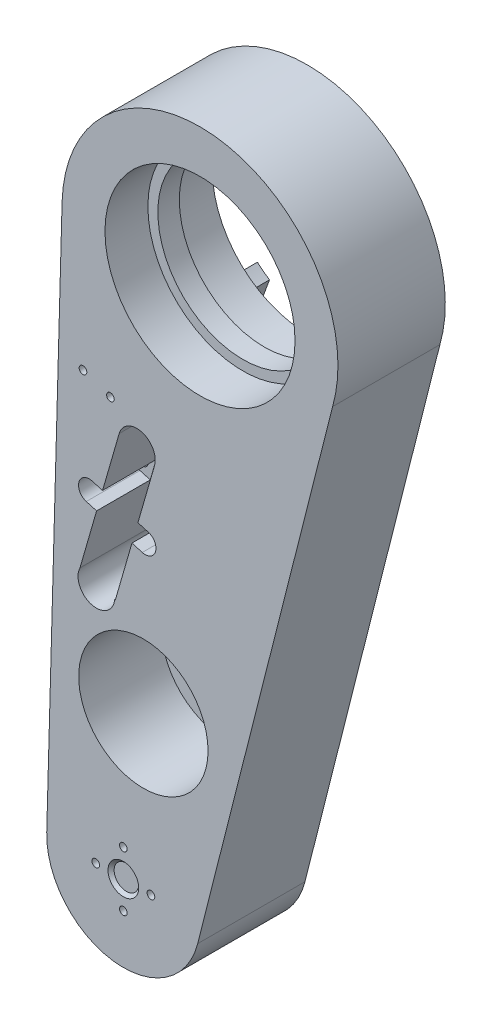
SolidWorks part; units mm, degrees
ref_plane "Ebene vorne" through (0, 0, 0) normal (0, 0, 1) x (1, 0, 0)
ref_plane "Ebene oben" through (0, 0, 0) normal (0, 1, 0) x (1, 0, 0)
ref_plane "Ebene rechts" through (0, 0, 0) normal (1, 0, 0) x (0, 0, -1)
sketch "Skizze1" plane through (0, 0, 0) normal (0, 0, 1) x (1, 0, 0)
  line L0 (-24.9904, 0.6931) -> (-19.9827, 181.2476)
  line L2 (68.9493, 170.3326) -> (24.2342, -6.1405)
  circle A0 centre (0, 0) radius 9
  circle A6 centre (0, 0) radius 25
  circle A7 centre (25, 180) radius 45
  circle A8 centre (25, 180) radius 28
  point P14 (0, 0)
  dimension "D1" = 18
  dimension "D3" = 50
  dimension "D5" = 90
  dimension "D7" = 56
  dimension "D4" = 180
  dimension "D6" = 25
extrude "Aufsatz-Linear austragen1" add sketch "Skizze1" along normal blind 35 contours A7 | A7 A6 | A6 A0 | A0 | A7 region at (11.8715, 85.5396, 0) region at (0.3368, 24.2906, 0) region at (68.6084, 168.9504, 0) region at (0, 0, 0)
sketch "Skizze2" plane through (0, 0, 35) normal (0, 0, 1) x (1, 0, 0)
  circle A0 centre (0, 0) radius 4
  dimension "D1" = 8
extrude "Schnitt-Linear austragen1" cut sketch "Skizze2" against normal blind 1 contours A0
chamfer "Fase1" distance 1 angle 45 1 edges at (4, 0, 35)
sketch "Skizze4" plane through (0, 0, 35) normal (0, 0, 1) x (1, 0, 0)
  arc A0 (-1.247, 8.9132) -> (-8.9132, 1.247) centre (0, 0) ccw
  circle A1 centre (9, 0) radius 1.25
  circle A2 centre (0, -9) radius 1.25
  circle A3 centre (-9, 0) radius 1.25
  circle A4 centre (0, 9) radius 1.25
  arc A5 (-8.9132, -1.247) -> (-1.247, -8.9132) centre (0, 0) ccw
  arc A6 (8.9132, 1.247) -> (1.247, 8.9132) centre (0, 0) ccw
  arc A7 (1.247, -8.9132) -> (8.9132, -1.247) centre (0, 0) ccw
  point P14 (0, 0)
  dimension "D1" = 18
  dimension "D2" = 4
  dimension "D3" = 2.5
extrude "Schnitt-Linear austragen2" cut sketch "Skizze4" against normal blind 15 contours A4 | A1 | A2 | A3 region at (0, 9, 35) region at (-9, 0, 35) region at (9, 0, 35) region at (0, -9, 35)
sketch "Skizze5" plane through (0, 0, 0) normal (0, 0, -1) x (-1, 0, 0)
  circle A0 centre (0, 0) radius 8
  circle A1 centre (8, 0) radius 1.25
  circle A2 centre (0, -8) radius 1.25
  circle A3 centre (-8, 0) radius 1.25
  circle A4 centre (0, 8) radius 1.25
  circle A5 centre (0, 0) radius 9.25
  point P14 (0, 0)
  dimension "D1" = 4
  dimension "D3" = 16
extrude "Schnitt-Linear austragen3" cut sketch "Skizze5" against normal blind 15 contours A0 A4 | A0 A4 | A0 A3 | A0 A3 | A0 A1 | A0 A1 | A0 A2 | A0 A2 region at (-7.4523, 0, 0) region at (-8.5125, 0, 0) region at (0, 7.4523, 0) region at (0, 8.5125, 0) region at (0, -8.5125, 0) region at (0, -7.4523, 0) region at (7.4523, 0, 0) region at (8.5125, 0, 0)
sketch "Skizze6" plane through (0, 0, 35) normal (0, 0, 1) x (1, 0, 0)
  line L1 (25, 182.9902) -> (0, 2.9902) construction
  circle A1 centre (6.5291, 50) radius 12.5
  dimension "D1" = 50
  dimension "D2" = 25
extrude "Schnitt-Linear austragen4" cut sketch "Skizze6" against normal blind 35
sketch "Skizze7" plane through (0, 0, 35) normal (0, 0, 1) x (1, 0, 0)
  circle A0 centre (6.5291, 50) radius 21.1
  dimension "D1" = 42.2
extrude "Schnitt-Linear austragen5" cut sketch "Skizze7" against normal offset from surface (27 mm away) 8 up to face at (19.0291, 50, 0)
sketch "Skizze8" plane through (0, 0, 8) normal (0, 0, 1) x (1, 0, 0)
  line L0 (6.5291, 50) -> (5.2968, 32.5434) construction
  arc A0 (5.7616, 67.4832) -> (-10.6728, 53.216) centre (6.5291, 50) ccw
  circle A1 centre (5.2968, 32.5434) radius 2
  circle A2 centre (-10.9274, 51.2323) radius 2
  circle A3 centre (7.7615, 67.4566) radius 2
  circle A4 centre (23.9857, 48.7677) radius 2
  arc A5 (24.0123, 50.7675) -> (9.7452, 67.2019) centre (6.5291, 50) ccw
  arc A6 (7.2966, 32.5168) -> (24.0123, 50.7675) centre (6.5291, 50) ccw
  arc A7 (-10.6728, 53.216) -> (3.3131, 32.7981) centre (6.5291, 50) ccw
  point P14 (6.5291, 50)
  dimension "D1" = 4
  dimension "D2" = 4
  dimension "D3" = 17.5
extrude "Schnitt-Linear austragen6" cut sketch "Skizze8" against normal blind 15 contours A4 | A3 | A1 | A2 | A2 | A4 region at (7.7615, 67.4566, 8) region at (-11.7533, 51.2906, 8) region at (23.1188, 48.8289, 8) region at (5.2968, 32.5434, 8)
sketch "Skizze9" plane through (0, 0, 0) normal (0, 0, -1) x (-1, 0, 0)
  circle A0 centre (-5.2968, 32.5434) radius 3.7
  circle A1 centre (-23.9857, 48.7677) radius 3.7
  circle A2 centre (-7.7615, 67.4566) radius 3.7
  circle A3 centre (10.9274, 51.2323) radius 3.7
  point P3 (-6.5291, 50)
  point P14 (-6.5291, 50)
  dimension "D1" = 7.4
  dimension "D2" = 4
extrude "Schnitt-Linear austragen7" cut sketch "Skizze9" against normal blind 4
sketch "Skizze10" plane through (0, 0, 35) normal (0, 0, 1) x (1, 0, 0)
  circle A0 centre (25, 180) radius 31
  dimension "D1" = 62
extrude "Schnitt-Linear austragen8" cut sketch "Skizze10" against normal blind 14
ref_plane "Ebene1" through (0, 0, 17.5) normal (0, 0, 1) x (1, 0, 0)
mirror "Spiegeln1" about plane through (0, 0, 17.5) normal (0, 0, 1) of "Schnitt-Linear austragen8"
sketch "Skizze11" plane through (0, 0, 0) normal (0, 0, 1) x (1, 0, 0)
  circle A1 centre (25.3541, 102.1802) radius 1.75
extrude "Schnitt-Linear austragen10" cut sketch "Skizze11" along normal blind 15
sketch "Skizze12" plane through (0, 0, 0) normal (0, 0, -1) x (-1, 0, 0)
  circle A1 centre (-25, 180) radius 32
  circle A4 centre (-9.1089, 136.6817) radius 2.1
  dimension "D3" = 64
extrude "Schnitt-Linear austragen11" cut sketch "Skizze12" against normal blind 20 contours A4 region at (9.1089, 136.6817, 0)
sketch "Sketch1" plane through (0, 0, 0) normal (0, 0, -1) x (-1, 0, 0)
  line L0 (-13.9792, 149.9577) -> (-5.0749, 153.2242) construction
  line L1 (-5.0749, 153.2242) -> (-22.2848, 146.9108) construction
  line L2 (-20.8178, 148.2745) -> (-16.2029, 135.6945)
  line L3 (-16.2029, 135.6945) -> (-25.776, 148.0094)
  line L4 (-25, 180) -> (-2.3558, 118.273) construction
  line L5 (-7.6743, 153.0961) -> (-3.0594, 140.5161)
  line L6 (-3.0594, 140.5161) -> (-3.721, 156.1001)
  circle A0 centre (-25, 180) radius 32
  dimension "D1" = 64
  dimension "D2" = 14
extrude "Boss-Extrude1" add sketch "Sketch1" along normal blind 5 contours A0 L3 L2 | A0 L5 L6 region at (20.9083, 143.9511, 0) region at (4.8096, 149.8568, 0)
sketch "Sketch2" plane through (0, 0, 0) normal (0, 0, -1) x (-1, 0, 0)
  circle A0 centre (-4.4016, 123.4949) radius 6
extrude "Cut-Extrude1" cut sketch "Sketch2" against normal blind 35
ref_plane "Plane1" through (0, 0, 30) normal (0, 0, -1) x (-1, 0, 0)
sketch "Sketch3" plane through (0, 0, 17.5) normal (0, 0, -1) x (-1, 0, 0)
  line L0 (14.468, 79.7139) -> (1.3635, 125.1573)
  line L1 (-10.1667, 121.8324) -> (2.9378, 76.3889)
  circle A0 centre (-4.4016, 123.4949) radius 6 construction
  circle A1 centre (-4.4016, 123.4949) radius 6
  circle A2 centre (8.7029, 78.0514) radius 6
  dimension "D1" = 12
extrude "Cut-Extrude2" cut sketch "Sketch3" along normal blind 8 contours A2 L0 L1 | A2 region at (-2.1506, 100.7731, 17.5) region at (-8.7029, 78.0514, 17.5)
sketch "Sketch4" plane through (0, 0, 35) normal (0, 0, 1) x (1, 0, 0)
  circle A2 centre (-8.7869, 78.1376) radius 6
extrude "Cut-Extrude3" cut sketch "Sketch4" against normal up to surface (25.5 mm away) up to face at (-2.9819, 97.8906, 9.5)
sketch "Skizze14" plane through (0, 0, 0) normal (0, 0, -1) x (-1, 0, 0)
  circle A0 centre (-59.0996, 191.6681) radius 1.65
  circle A1 centre (4.4449, 200.7123) radius 1.655
  circle A2 centre (-26.5283, 29.0181) radius 1.65
  circle A3 centre (18.5472, 35.4337) radius 1.65
extrude "Schnitt-Linear austragen12" cut sketch "Skizze14" against normal blind 15
sketch "Skizze16" plane through (0, 0, 35) normal (0, 0, 1) x (1, 0, 0)
  circle A3 centre (-13.1725, 137.1867) radius 1.25
  circle A4 centre (-4.2165, 134.0181) radius 1.25
extrude "Schnitt-Linear austragen14" cut sketch "Skizze16" against normal blind 6
sketch "Skizze17" plane through (0, 0, 21) normal (0, 0, 1) x (1, 0, 0)
  circle A0 centre (25, 180) radius 27.75
  dimension "D1" = 55.5
extrude "Schnitt-Linear austragen15" cut sketch "Skizze17" against normal blind 10
sketch "Sketch5" plane through (0, 0, 35) normal (0, 0, 1) x (1, 0, 0)
  line L0 (-14.1424, 80.8429) -> (-1.3635, 125.1573)
  line L1 (-1.3635, 125.1573) -> (10.1667, 121.8324)
  line L2 (10.1667, 121.8324) -> (-2.6122, 77.5179)
  line L3 (10.1667, 121.8324) -> (-2.9378, 76.3889) construction
  line L4 (-7.7529, 103.0001) -> (-14.4789, 104.9397) construction
  line L5 (-14.4789, 104.9397) -> (10.5032, 97.7356) construction
  line L6 (-6.7832, 106.3631) -> (-10.1461, 107.3329)
  line L7 (-8.7227, 99.6371) -> (-12.0857, 100.6069)
  line L8 (-1.9878, 101.3376) -> (0.7272, 110.7527) construction
  line L9 (3.7772, 99.6752) -> (10.5032, 97.7356) construction
  line L10 (2.8075, 96.3122) -> (6.1704, 95.3424)
  line L11 (4.747, 103.0381) -> (8.11, 102.0684)
  line L12 (-14.1424, 80.8429) -> (-2.6122, 77.5179)
  line L13 (4.4016, 123.4949) -> (-8.8685, 77.8571) construction
  circle A0 centre (-11.1159, 103.9699) radius 3.5
  circle A1 centre (7.1402, 98.7054) radius 3.5
  circle A2 centre (-11.1159, 103.9699) radius 1.65
  circle A3 centre (7.1402, 98.7054) radius 1.65
  circle M8 centre (-8.7869, 78.1376) radius 6
  circle M9 centre (4.4016, 123.4949) radius 6
  dimension "D1" = 7
extrude "Cut-Extrude4" cut sketch "Sketch5" against normal up to surface (17.5 mm away) contours L12 L2 L0 M8 M9 | A0 A2 | A0 L7 L0 | A0 L0 L6 | L2 A1 L11 | A1 A3 | L10 A1 L2 region at (-2.1317, 100.8027, 35) region at (-9.2573, 100.6049, 35) region at (-7.751, 105.8285, 35) region at (-9.4715, 100.9928, 35) region at (3.7753, 96.8468, 35) region at (5.2816, 102.0703, 35) region at (5.4958, 101.6824, 35) up to face at (-2.3062, 94.2289, 17.5)
sketch "Sketch6" plane through (0, 0, 35) normal (0, 0, 1) x (1, 0, 0)
  circle A0 centre (-11.1159, 103.9699) radius 1.65
  circle A1 centre (7.1402, 98.7054) radius 1.65
extrude "Cut-Extrude5" cut sketch "Sketch6" against normal up to surface (25.5 mm away) up to face at (-4.6765, 93.8523, 9.5)
